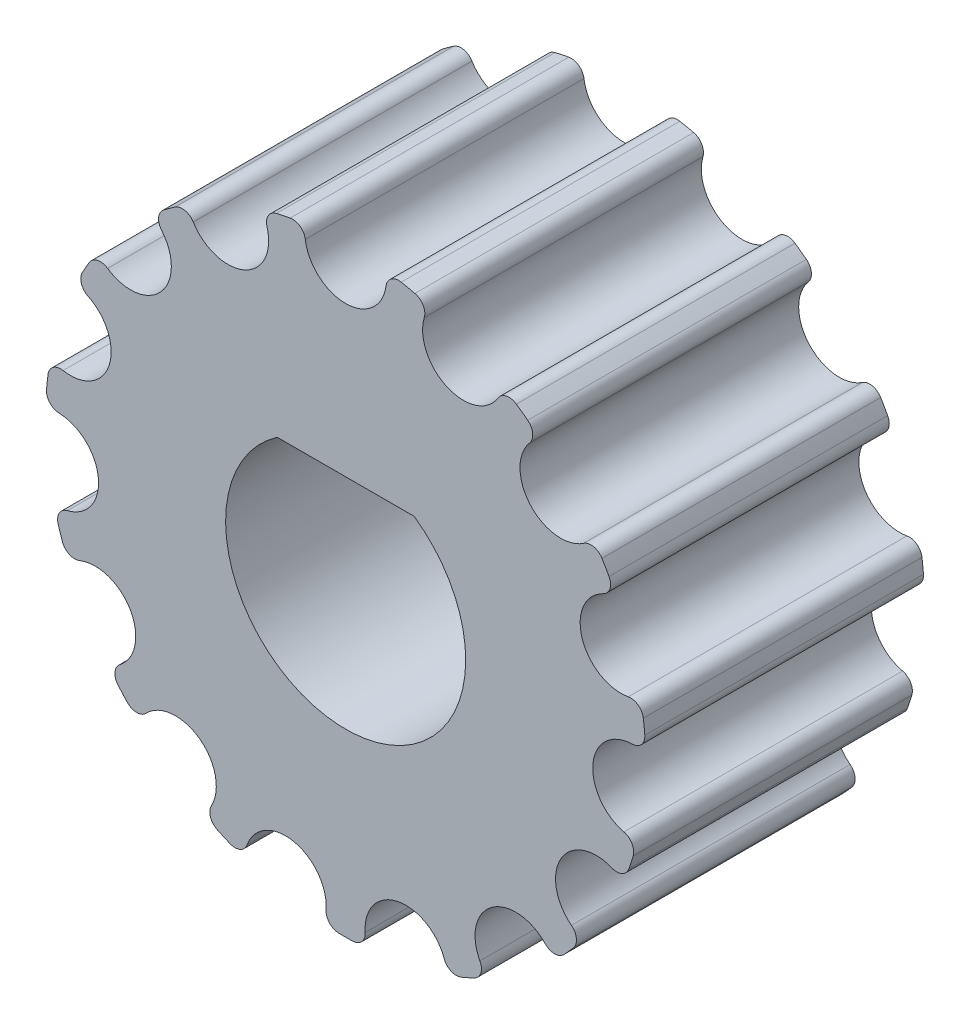
SolidWorks part; units mm, degrees
ref_plane "Ebene vorne" through (0, 0, 0) normal (0, 0, 1) x (1, 0, 0)
ref_plane "Ebene oben" through (0, 0, 0) normal (0, 1, 0) x (1, 0, 0)
ref_plane "Ebene rechts" through (0, 0, 0) normal (1, 0, 0) x (0, 0, -1)
sketch "Skizze1" plane through (0, 0, 0) normal (0, 0, 1) x (1, 0, 0)
  circle A0 centre (0, 0) radius 7
  dimension "D1" = 14
extrude "Aufsatz-Linear austragen1" add sketch "Skizze1" along normal mid plane 6.5
sketch "Skizze2" plane through (0, 0, 0) normal (0, 0, 1) x (1, 0, 0)
  line L0 (0, 0) -> (0, 7) construction
  line L1 (0.95, 6.75) -> (0.95, 7)
  line L2 (0.95, 7) -> (-0.95, 7)
  line L3 (-0.95, 7) -> (-0.95, 6.75)
  circle A0 centre (0, 0) radius 7 construction
  arc A1 (-0.95, 6.75) -> (0.95, 6.75) centre (0, 6.75) ccw
  point P9 (-0.95, 6.4387)
  point P12 (0, 7)
  dimension "D1" = 1.9
  dimension "D2" = 1.2
extrude "Schnitt-Linear austragen1" cut sketch "Skizze2" against normal through all both and the other way through all
fillet "Verrundung2" radius 0.3 2 edges at (0.95, 6.9352, 0) (-0.95, 6.9352, 0)
pattern_circular "Kreismuster1" count 15 over 360 about axis through (0, 0, 3.25) along (0, 0, -1) of "Schnitt-Linear austragen1", "Verrundung2"
ref_axis "Achse1" through (0, 0, -3.575) along (0, 0, 1)
sketch "Skizze3" plane through (0, 0, 0) normal (0, 0, 1) x (1, 0, 0)
  line L0 (1.5, 2) -> (-1.5, 2) construction
  line L1 (1.5969, 2.3) -> (-1.5969, 2.3)
  arc A0 (-1.5, 2) -> (1.5, 2) centre (0, 0) ccw construction
  arc A1 (-1.5969, 2.3) -> (1.5969, 2.3) centre (0, 0) ccw
  point P5 (2.2578, 1.0734)
  dimension "D1" = 5
  dimension "D2" = 4.5
  dimension "D3" = 0.3
extrude "Schnitt-Linear austragen2" cut sketch "Skizze3" against normal through all both and the other way through all
